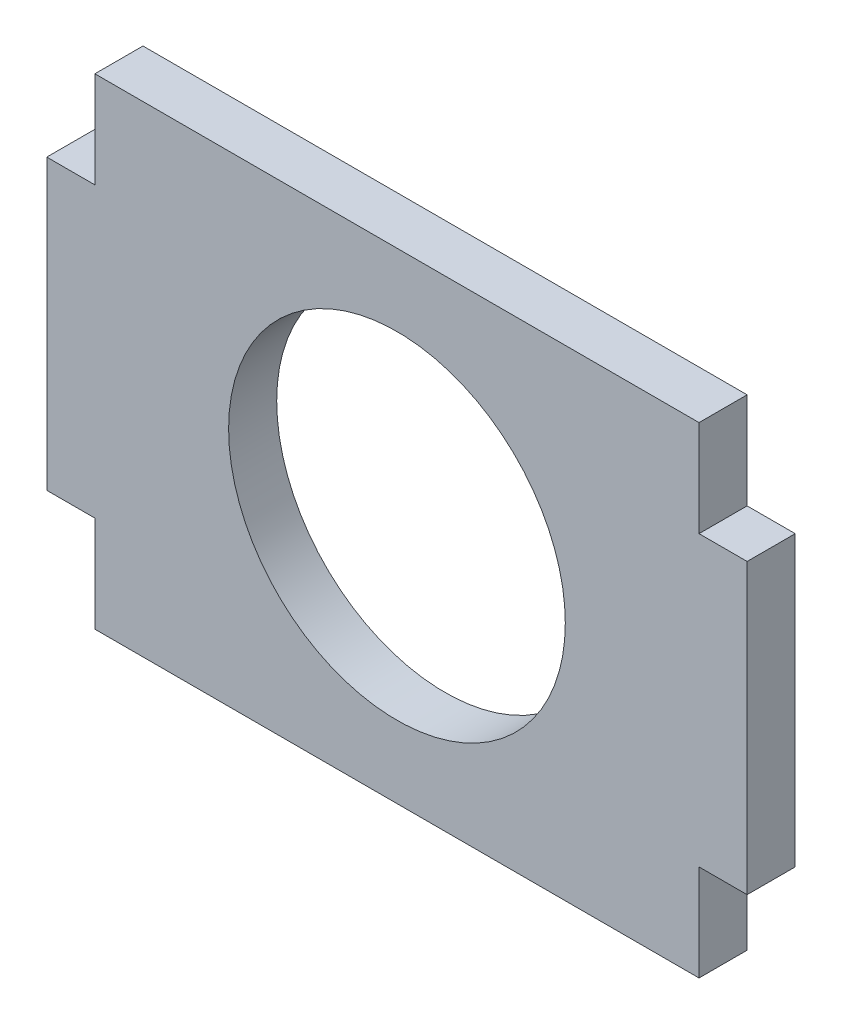
SolidWorks part; units mm, degrees
material "6061-T6 (SS)"
ref_plane "Front Plane" through (0, 0, 0) normal (0, 0, 1) x (1, 0, 0)
ref_plane "Top Plane" through (0, 0, 0) normal (0, 1, 0) x (1, 0, 0)
ref_plane "Right Plane" through (0, 0, 0) normal (1, 0, 0) x (0, 0, -1)
sketch "Sketch1" plane through (0, 0, 0) normal (0, 0, 1) x (1, 0, 0)
  line L0 (-23.114, -9.525) -> (-23.114, 9.525)
  line L1 (23.114, -9.525) -> (23.114, 9.525)
  line L2 (23.114, 9.525) -> (19.939, 9.525)
  line L3 (19.939, 9.525) -> (19.939, 15.875)
  line L4 (19.939, 15.875) -> (-19.939, 15.875)
  line L5 (-19.939, 15.875) -> (-19.939, 9.525)
  line L6 (-19.939, 9.525) -> (-23.114, 9.525)
  line L7 (-23.114, -9.525) -> (-19.939, -9.525)
  line L8 (-19.939, -9.525) -> (-19.939, -15.875)
  line L9 (-19.939, -15.875) -> (19.939, -15.875)
  line L10 (19.939, -15.875) -> (19.939, -9.525)
  line L11 (19.939, -9.525) -> (23.114, -9.525)
  line L12 (0, 0) -> (0, -15.875) construction
  line L13 (0, 0) -> (0, 15.875) construction
  circle A0 centre (0, 0) radius 11.1125
  point P6 (-23.114, 0)
  point P9 (23.114, 0)
  dimension "D1" = 22.225
  dimension "D2" = 39.878
  dimension "D3" = 3.175
  dimension "D4" = 6.35
  dimension "D5" = 31.75
extrude "Boss-Extrude1" add sketch "Sketch1" along normal blind 3.175
